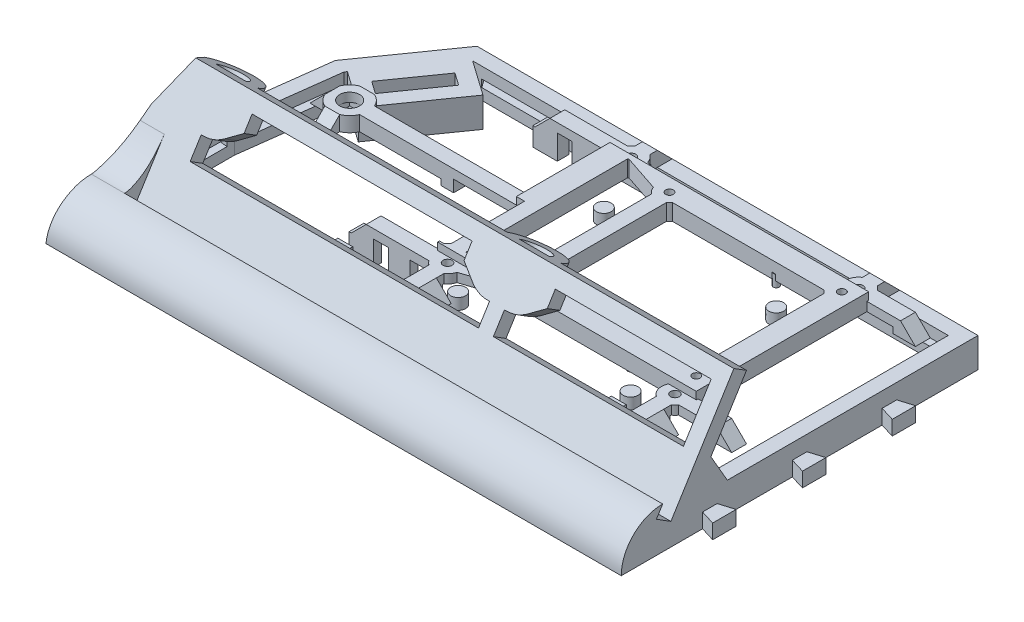
SolidWorks part; units mm, degrees
ref_plane "Front Plane" through (0, 0, 0) normal (0, 0, 1) x (1, 0, 0)
ref_plane "Top Plane" through (0, 0, 0) normal (0, 1, 0) x (1, 0, 0)
ref_plane "Right Plane" through (0, 0, 0) normal (1, 0, 0) x (0, 0, -1)
sketch "Sketch1" plane through (0, 0, 0) normal (1, 0, 0) x (0, 0, -1)
  line L0 (-2.7566, 6.4392) -> (-12.99, 6.4392) construction
  line L1 (-16.6958, -7.5) -> (103.3042, -7.5)
  line L2 (103.3042, -7.5) -> (103.3042, 2.5)
  line L3 (103.3042, 2.5) -> (18.9883, 2.5)
  line L4 (13.451, 12.0908) -> (25.437, 31.2723)
  line L5 (25.437, 31.2723) -> (21.1968, 33.9219)
  line L6 (21.1968, 33.9219) -> (0, 0)
  line L7 (0, 0) -> (-4.8763, 3.047)
  line L8 (25.437, 31.2723) -> (19.444, 21.6816) construction
  line L9 (-2.7566, 6.4392) -> (-4.8763, 3.047)
  line L10 (19.444, 21.6816) -> (13.451, 12.0908) construction
  line L11 (13.451, 12.0908) -> (7.4581, 2.5) construction
  line L12 (18.9883, 2.5) -> (7.4581, 2.5) construction
  line L13 (13.451, 12.0908) -> (18.9883, 2.5)
  arc A0 (-2.7566, 6.4392) -> (-16.6958, -7.5) centre (-2.7566, -7.5) ccw
  dimension "D10" = 58
  dimension "D1" = 4
  dimension "D2" = 5.75
  dimension "D3" = 40
  dimension "D4" = 7.5
  dimension "D5" = 120
  dimension "D6" = 10
  dimension "D7" = 5
  dimension "D8" = 60
  dimension "D9" = 58
extrude "Boss-Extrude1" add sketch "Sketch1" along normal blind 181 and the other way blind 12.5 contours L6 L7 L9 L1 L2 L3 L4 region at (0, 0.3543, -38.4922)
ref_plane "Plane1" through (0, -2.5, 0) normal (0, 1, 0) x (1, 0, 0)
sketch "Sketch4" plane through (0, 0, 0) normal (-1, 0, 0) x (0, 0, 1)
  line L0 (-21.1968, 33.9219) -> (0, 0) construction
  line L2 (-10.5984, 16.961) -> (0, 0)
  line L3 (0, 0) -> (4.8763, 3.047)
  line L4 (4.8763, 3.047) -> (2.7566, 6.4392)
  arc A0 (16.6958, -7.5) -> (2.7566, 6.4392) centre (2.7566, -7.5) ccw construction
  spline S0 degree 3 poles (2.7566, 6.4392) (0.7239, 6.4392) (-5.4135, 8.6634) (-10.5984, 16.961) knots 0 0 0 0 1 1 1 1
extrude "Boss-Extrude2" add sketch "Sketch4" along normal blind 12.5
sketch "Sketch3" plane through (0, 0, 0) normal (0, 0, 1) x (1, 0, 0)
  line L0 (0, 0) -> (0, 33.9219) construction
  line L1 (0, 33.9219) -> (-6.9073, 21.0423)
  line L2 (0, 33.9219) -> (-12.5, 33.9219)
  line L3 (-12.5, 33.9219) -> (181, 33.9219) construction
  line L4 (-6.9073, 21.0423) -> (-11.1296, 7.0505)
  line L5 (-12.5, 33.9219) -> (-12.5, -7.5)
  line L6 (-12.5, -7.5) -> (181, -7.5) construction
  line L7 (-11.1296, 7.0505) -> (-12.5, -7.5)
  arc A0 (-10.9929, 7.5036) -> (-11.174, 6.5794) centre (-11.1296, 7.0505) cw construction
  arc A1 (-6.6836, 21.4593) -> (-7.044, 20.5892) centre (-6.9073, 21.0423) cw construction
  spline S0 degree 2 poles (0, 33.9219) (-12.5, 15.097) (-12.5, -7.5) knots 0 0 0 1 1 1 construction
extrude "Cut-Extrude1" cut sketch "Sketch3" against normal blind 80 and the other way blind 80 contours L7 L4 L1 L2 L5 region at (-8.7764, 23.2458, 0)
sketch "Sketch5" plane through (0, 0, 0) normal (0, 1, 0) x (1, 0, 0)
  line B0 (-12.5, 103.3042) -> (12.5, 103.3042)
  line B1 (12.5, 103.3042) -> (-7.1997, 75.3013)
  line B2 (-7.1997, 75.3013) -> (-11.5261, 41.3377)
  line B3 (-11.5261, 41.3377) -> (-12.5, 7.1136)
  line B4 (-12.5, 103.3042) -> (-12.5, 7.1136)
sketch_block_instance "Block5-1"
sketch_block "Block5" parameters "D1"=25
extrude "Cut-Extrude2" cut sketch "Sketch5" against normal blind 10 and the other way blind 80
sketch "Sketch16" plane through (0, -7.5, 0) normal (0, -1, 0) x (1, 0, 0)
  line L0 (185.9, -9.1541) -> (181, -10.6541)
  line L1 (181, 16.6958) -> (181, -103.3042) construction
  line L2 (185.9, -9.1541) -> (185.9, -17.0541)
  line L3 (185.9, -17.0541) -> (181, -15.5541)
  line L4 (185.9, -69.5543) -> (181, -71.0543)
  line L5 (185.9, -69.5543) -> (185.9, -77.4543)
  line L6 (185.9, -77.4543) -> (181, -75.9543)
  line L7 (181, -40.8542) -> (185.9, -39.3542)
  line L8 (185.9, -39.3542) -> (185.9, -47.2542)
  line L9 (185.9, -47.2542) -> (181, -45.7542)
  line L10 (181, 16.6958) -> (185.9, -13.1041) construction
  line L11 (185.9, -13.1041) -> (185.9, -43.3042) construction
  line L12 (185.9, -43.3042) -> (185.9, -73.5043) construction
  line L13 (185.9, -73.5043) -> (181, -103.3042) construction
  line L14 (185.9, -43.3042) -> (181, -43.3042) construction
  line L15 (181, -10.6541) -> (181, -15.5541)
  line L16 (181, -40.8542) -> (181, -45.7542)
  line L17 (181, -71.0543) -> (181, -75.9543)
  line L18 (-12.5, 16.6958) -> (181, 16.6958) construction
  dimension "D1" = 4.9
  dimension "D2" = 4.9
  dimension "D3" = 7.9
  dimension "D4" = 29.7999
extrude "Boss-Extrude4" add sketch "Sketch16" against normal blind 4.9
sketch "Sketch18" plane through (0, 2.5, 0) normal (0, 1, 0) x (1, 0, 0)
  line L0 (20.6722, 88.851) -> (9.1647, 72.4932) construction
  line L1 (9.1647, 72.4932) -> (5.0753, 75.3701) construction
  line L2 (5.0753, 75.3701) -> (16.5828, 91.7279) construction
  line L3 (16.5828, 91.7279) -> (20.6722, 88.851) construction
  line L6 (12.5, 103.3042) -> (22.7236, 96.112) construction
  line L7 (22.7236, 96.112) -> (18.6275, 90.2894) construction
  line L8 (12.5, 103.3042) -> (-7.1997, 75.3013) construction
  line L9 (7.12, 73.9316) -> (3.0239, 68.1091) construction
  line L10 (3.0239, 68.1091) -> (-7.1997, 75.3013) construction
  line L11 (5.0056, 75.358) -> (16.5707, 91.7975)
  line L12 (16.5707, 91.7975) -> (20.7419, 88.8631)
  line L13 (20.7419, 88.8631) -> (9.1768, 72.4235)
  line L16 (9.1768, 72.4235) -> (5.0056, 75.358)
  line L18 (27.3633, 88.437) -> (27.3633, 77.0251) construction
  dimension "D1" = 20
  dimension "D2" = 5
  dimension "D3" = 12.5
  dimension "D5" = 35.126
  dimension "D4" = 0.05
extrude "Cut-Extrude15" cut sketch "Sketch18" against normal blind 5.1
sketch "Sketch19" plane through (0, 33.9219, -21.1968) normal (0, 0.848, -0.5299) x (1, 0, 0)
  line L0 (-11.5582, 5) -> (181, 5) construction
  line L1 (-1.421, 5) -> (2.529, 5)
  line L2 (12.629, 5) -> (16.579, 5)
  line L3 (100.579, 5) -> (104.529, 5)
  line L5 (114.629, 5) -> (118.579, 5)
  arc A0 (16.579, 5) -> (-1.421, 5) centre (7.579, 5) ccw
  arc A1 (12.629, 5) -> (2.529, 5) centre (7.579, 5) ccw
  arc A2 (114.629, 5) -> (104.529, 5) centre (109.579, 5) ccw
  arc A3 (100.579, 5) -> (118.579, 5) centre (109.579, 5) cw
  dimension "D1" = 10.1
  dimension "D2" = 18
  dimension "D4" = 102
  dimension "D3" = 3.95
extrude "Boss-Extrude5" add sketch "Sketch19" against normal blind 7.6 separate body
sketch "Sketch21" plane through (0, -2.6496, -4.2402) normal (0, -0.5299, -0.848) x (-1, 0, 0)
  line L0 (-7.579, 32.4) -> (-7.579, 29.4)
  line L1 (-16.579, 32.4) -> (1.421, 32.4) construction
  line L2 (-16.579, 32.4) -> (-15.2457, 31.4)
  line L3 (-7.579, 29.4) -> (-9.2457, 29.4)
  line L5 (-16.579, 32.4) -> (-7.579, 32.4)
  arc A0 (-9.2457, 29.4) -> (-15.2457, 31.4) centre (-9.2457, 39.4) cw
  dimension "D2" = 10
  dimension "D1" = 3
revolve "Revolve1" add sketch "Sketch21" angle 180 about L0 reverse direction yes
sketch "Sketch22" plane through (0, 0, 0) normal (1, 0, 0) x (0, 0, -1)
  line L0 (21.1968, 33.9219) -> (71.4824, 2.5) construction
  line L1 (103.3042, 2.5) -> (18.9883, 2.5) construction
  line L2 (33.0694, 26.5031) -> (25.437, 31.2723) construction
  point P7 (25.437, 31.2723)
  point P10 (71.4824, 2.5)
  dimension "D1" = 54.2957
sketch "Sketch24" plane through (0, 33.9219, -21.1968) normal (0, 0.848, -0.5299) x (1, 0, 0)
  line L0 (7.579, 5) -> (7.579, 128.2627) construction
  line L6 (2.529, 5) -> (12.629, 5) construction
  point P3 (7.579, 5)
sketch "Sketch25" plane through (0, 2.5, 0) normal (0, 1, 0) x (1, 0, 0)
  line L0 (16.5707, 91.7975) -> (9.1768, 72.4235) construction
  line L1 (7.579, -169584.1822) -> (7.579, 169739.5889) construction
  point P6 (12.8737, 82.1105)
  dimension "D1" = 5.2947
sketch "Sketch26" plane through (0, -2.6496, -4.2402) normal (0, -0.5299, -0.848) x (-1, 0, 0)
  line L0 (-109.579, 32.4) -> (-109.579, 29.4)
  line L2 (-118.579, 32.4) -> (-117.2457, 31.4)
  line L3 (-109.579, 29.4) -> (-111.2457, 29.4)
  line L5 (-118.579, 32.4) -> (-109.579, 32.4)
  line L6 (-118.579, 32.4) -> (-100.579, 32.4) construction
  arc A0 (-111.2457, 29.4) -> (-117.2457, 31.4) centre (-111.2457, 39.4) cw
  dimension "D2" = 10
  dimension "D1" = 3
revolve "Revolve2" add sketch "Sketch26" angle 180 about L0 reverse direction yes
sketch "Sketch33" plane through (0, -2.6496, -4.2402) normal (0, -0.5299, -0.848) x (-1, 0, 0)
  line L1 (-176, 35) -> (-123.579, 35)
  line L2 (-176, 35) -> (-176, 17.3815)
  line L3 (-176, 17.3815) -> (-112.079, 17.3815)
  line L4 (-21.579, 35) -> (-21.579, 29.9)
  line L5 (-118.579, 40) -> (-181, 40) construction
  line L6 (9.6086, 17.3815) -> (-181, 17.3815) construction
  line L7 (-123.579, 35) -> (-123.579, 29.9)
  line L8 (-118.579, 32.4) -> (-118.579, 40) construction
  line L9 (-95.579, 29.9) -> (-95.579, 35)
  line L10 (-100.579, 32.4) -> (-100.579, 40) construction
  line L11 (-123.579, 29.9) -> (-118.9124, 26.4)
  line L12 (-112.9124, 24.4) -> (-112.079, 24.4)
  line L13 (-100.2457, 26.4) -> (-95.579, 29.9)
  line L14 (-123.579, 29.9) -> (-95.579, 29.9) construction
  line L15 (-118.579, 32.4) -> (-117.2457, 31.4) construction
  line L16 (-100.579, 32.4) -> (-101.9124, 31.4) construction
  line L17 (-107.9124, 29.4) -> (-111.2457, 29.4) construction
  line L18 (2.038, 26.6128) -> (0.1213, 30.8271) construction
  line L19 (-112.079, 24.4) -> (-112.079, 17.3815)
  line L20 (-107.079, 24.4) -> (-106.2457, 24.4)
  line L21 (-107.079, 24.4) -> (-107.079, 17.3815)
  line L22 (-107.079, 17.3815) -> (-10.079, 17.3815)
  line L23 (-21.579, 29.9) -> (-16.9124, 26.4)
  line L24 (-10.9124, 24.4) -> (-10.079, 24.4)
  line L25 (-10.079, 24.4) -> (-10.079, 17.3815)
  line L26 (-5.9124, 29.4) -> (-9.2457, 29.4) construction
  line L27 (-16.579, 32.4) -> (-15.2457, 31.4) construction
  line L28 (-7.579, 29.4) -> (-7.579, 17.3815) construction
  line L29 (-16.579, 32.4) -> (-16.579, 40) construction
  line L30 (2.038, 26.6128) -> (1.7543, 26.4)
  line L31 (-4.2457, 24.4) -> (-5.079, 24.4)
  line L32 (-5.079, 24.4) -> (-5.079, 17.3815)
  line L33 (4.4675, 17.3815) -> (2.1913, 26.2757)
  line L34 (2.1913, 26.2757) -> (2.038, 26.6128)
  line L35 (6.9073, 27.9369) -> (9.6086, 17.3815) construction
  line L36 (1.421, 40) -> (6.9073, 27.9369) construction
  line L37 (2.1913, 26.2757) -> (6.9073, 27.9369) construction
  line L38 (1.421, 32.4) -> (0.0876, 31.4) construction
  line L39 (-95.579, 35) -> (-21.579, 35)
  line L40 (-181, 17.3815) -> (-181, 40) construction
  arc A0 (-106.2457, 24.4) -> (-100.2457, 26.4) centre (-106.2457, 34.4) ccw
  arc A1 (-118.9124, 26.4) -> (-112.9124, 24.4) centre (-112.9124, 34.4) ccw
  arc A2 (1.7543, 26.4) -> (-4.2457, 24.4) centre (-4.2457, 34.4) cw
  arc A3 (-16.9124, 26.4) -> (-10.9124, 24.4) centre (-10.9124, 34.4) ccw
  arc A4 (3.431, 21.4318) -> (0.1213, 30.8271) centre (2.1913, 26.2757) ccw construction
  point P18 (-95.579, 32.45)
  point P52 (-0.9124, 24.4)
  point P55 (-14.2457, 24.4)
  point P59 (6.9073, 27.9369)
  line M30 (-181, 17.3815) -> (9.6086, 17.3815)
  dimension "D3" = 10
  dimension "D11" = 10
  dimension "D1" = 5
  dimension "D2" = 5
  dimension "D4" = 5
  dimension "D5" = 5
  dimension "D6" = 5
  dimension "D7" = 5
  dimension "D8" = 5
  dimension "D9" = 2.5
  dimension "D10" = 5
  dimension "D12" = 5
  dimension "D13" = 5
  dimension "D14" = 5
extrude "Cut-Extrude21" cut sketch "Sketch33" against normal blind 5 contours A3 L23 L4 L39 L9 L13 A0 L20 L21 L25 L24 M30 | A1 L11 L7 L1 L2 L19 L12 M30 region at (58.579, 19.0794, -17.818) region at (146.6729, 19.2071, -17.8978)
sketch "Sketch35" plane through (0, 2.5, 0) normal (0, 1, 0) x (1, 0, 0)
  line L0 (12.5, 103.3042) -> (-7.1997, 75.3013)
  line L1 (-7.1997, 75.3013) -> (-11.5261, 41.3377)
  line L2 (12.5, 103.3042) -> (181, 103.3042)
  line L3 (181, 103.3042) -> (181, 23.9883)
  line L4 (-11.5582, 18.9883) -> (181, 18.9883) construction
  line L5 (-11.5582, 23.9883) -> (-11.5261, 41.3377)
  line L6 (-11.5582, 18.9883) -> (-11.5582, 40.2092) construction
  line L9 (181, 23.9883) -> (-11.5582, 23.9883)
  point P11 (-11.5582, 23.9883)
  point P13 (0, 0)
  dimension "D1" = 5
extrude "Boss-Extrude7" add sketch "Sketch35" along normal blind 5
sketch "Sketch34" plane through (0, -7.5, 0) normal (0, -1, 0) x (1, 0, 0)
  line L0 (115.825, -18.9883) -> (115.825, -103.3042) construction
  line L1 (65.65, -26.2462) -> (166, -26.2462) construction
  line L2 (65.65, -26.2462) -> (65.65, -44.2462) construction
  line L3 (65.65, -96.0462) -> (166, -96.0462) construction
  line L4 (166, -26.2462) -> (166, -96.0462) construction
  line L5 (181, -75.9543) -> (181, -103.3042) construction
  line L6 (65.65, -26.2462) -> (166, -96.0462) construction
  line L7 (12.5, -103.3042) -> (181, -103.3042) construction
  line L9 (21.65, -64.2962) -> (21.65, -69.6462) construction
  line L10 (53.45, -69.6462) -> (53.45, -98.0462) construction
  line L11 (65.65, -44.2462) -> (58.05, -44.2462) construction
  line L12 (65.45, -26.0462) -> (166.2, -26.0462)
  line L13 (65.65, -87.5462) -> (58.05, -87.5462) construction
  line L14 (166.2, -26.0462) -> (166.2, -96.2462)
  line L15 (53.45, -24.2462) -> (58.05, -24.2462) construction
  line L16 (53.45, -24.2462) -> (53.45, -52.6462) construction
  line L17 (53.45, -98.0462) -> (58.05, -98.0462) construction
  line L18 (58.05, -24.2462) -> (58.05, -44.2462) construction
  line L19 (21.65, -52.6462) -> (53.45, -52.6462) construction
  line L20 (21.65, -52.6462) -> (21.65, -57.9962) construction
  line L21 (21.65, -69.6462) -> (53.45, -69.6462) construction
  line L22 (65.45, -96.2462) -> (166.2, -96.2462)
  line L23 (21.65, -57.9962) -> (8.65, -57.9962) construction
  line L24 (65.45, -87.7462) -> (65.45, -96.2462)
  line L25 (21.65, -64.2962) -> (8.65, -64.2962) construction
  line L26 (8.65, -57.9962) -> (8.65, -64.2962) construction
  line L27 (58.05, -87.5462) -> (58.05, -98.0462) construction
  line L28 (65.65, -87.5462) -> (65.65, -96.0462) construction
  line L29 (65.45, -87.7462) -> (58.25, -87.7462)
  line L30 (58.25, -87.7462) -> (58.25, -98.2462)
  line L31 (53.25, -98.2462) -> (58.25, -98.2462)
  line L32 (53.25, -69.8462) -> (53.25, -98.2462)
  line L33 (21.45, -69.8462) -> (53.25, -69.8462)
  line L34 (21.45, -64.4962) -> (21.45, -69.8462)
  line L35 (21.45, -64.4962) -> (8.45, -64.4962)
  line L36 (8.45, -57.7962) -> (8.45, -64.4962)
  line L37 (21.45, -57.7962) -> (8.45, -57.7962)
  line L38 (21.45, -52.4462) -> (21.45, -57.7962)
  line L39 (21.45, -52.4462) -> (53.25, -52.4462)
  line L40 (53.25, -24.0462) -> (53.25, -52.4462)
  line L41 (53.25, -24.0462) -> (58.25, -24.0462)
  line L42 (58.25, -24.0462) -> (58.25, -44.0462)
  line L43 (65.45, -44.0462) -> (58.25, -44.0462)
  line L44 (65.45, -26.0462) -> (65.45, -44.0462)
  point P9 (115.825, -61.1462)
  point P10 (66.8992, -96.0462)
  point P12 (0, 0)
  point P15 (115.825, -61.1462)
  point P18 (28.3358, -52.7545)
  point P19 (0, 0)
  point P53 (0, 0)
  dimension "D1" = 100.35
  dimension "D2" = 69.8
  dimension "D3" = 18
  dimension "D4" = 8.5
  dimension "D5" = 7.6
  dimension "D6" = 12.2
  dimension "D7" = 2
  dimension "D8" = 2
  dimension "D9" = 17
  dimension "D10" = 28.4
  dimension "D11" = 6.3
  dimension "D12" = 5.35
  dimension "D13" = 13
  dimension "D14" = 44
  dimension "D15" = 15
  dimension "D16" = 0.2
extrude "Cut-Extrude23" cut sketch "Sketch34" against normal blind 12
sketch "Sketch36" plane through (0, 4.5, 0) normal (0, 1, 0) x (1, 0, 0)
  line L0 (75.625, 92.0462) -> (75.625, 30.2462) construction
  line L1 (65.625, 96.0462) -> (166.025, 96.0462) construction
  line L2 (65.625, 96.0462) -> (65.625, 26.2462) construction
  line L3 (65.625, 26.2462) -> (166.025, 26.2462) construction
  line L4 (166.025, 96.0462) -> (166.025, 26.2462) construction
  line L5 (75.625, 92.0462) -> (152.125, 92.0462) construction
  line L6 (152.125, 92.0462) -> (152.125, 30.2462) construction
  line L7 (152.125, 30.2462) -> (75.625, 30.2462) construction
  line L8 (65.625, 61.1462) -> (75.625, 61.1462) construction
  line L9 (65.625, 96.0462) -> (166.025, 26.2462) construction
  line L10 (166.2, 96.2462) -> (65.45, 26.0462) construction
  circle A0 centre (75.625, 92.0462) radius 1.5
  circle A1 centre (152.125, 92.0462) radius 1.5
  circle A2 centre (75.625, 30.2462) radius 1.5
  circle A3 centre (152.125, 30.2462) radius 1.5
  point P16 (115.825, 61.1462)
  point P17 (115.825, 61.1462)
  dimension "D3" = 3
  dimension "D1" = 100.4
  dimension "D2" = 69.8
  dimension "D4" = 61.8
  dimension "D5" = 76.5
  dimension "D6" = 13.9
  dimension "D7" = 10
extrude "Cut-Extrude25" cut sketch "Sketch36" along normal blind 10
sketch "Sketch37" plane through (0, 7.5, 0) normal (0, 1, 0) x (1, 0, 0)
  circle A0 centre (75.625, 92.0462) radius 3
  circle A1 centre (152.125, 92.0462) radius 3
  circle A2 centre (152.125, 30.2462) radius 3
  circle A3 centre (75.625, 30.2462) radius 3
  dimension "D1" = 6
sketch "Sketch39" plane through (0, 7.5, 0) normal (0, 1, 0) x (1, 0, 0)
  line L0 (75.625, 92.0462) -> (152.125, 30.2462) construction
  line L1 (70.375, 90.1462) -> (157.375, 90.1462)
  line L2 (70.375, 90.1462) -> (70.375, 32.1462)
  line L3 (70.375, 32.1462) -> (157.375, 32.1462)
  line L4 (157.375, 90.1462) -> (157.375, 32.1462)
  line L6 (157.375, 90.1462) -> (70.375, 32.1462) construction
  point P4 (113.875, 61.1462)
  point P5 (113.875, 61.1462)
  dimension "D1" = 87
  dimension "D2" = 58
extrude "Boss-Extrude8" add sketch "Sketch39" along normal blind 2.5
sketch "Sketch40" plane through (0, 10, 0) normal (0, 1, 0) x (1, 0, 0)
  line L1 (94.875, 85.6462) -> (152.875, 85.6462) construction
  line L2 (94.875, 85.6462) -> (94.875, 36.6462) construction
  line L3 (94.875, 36.6462) -> (152.875, 36.6462) construction
  line L4 (152.875, 85.6462) -> (152.875, 36.6462) construction
  line L6 (157.375, 90.1462) -> (70.375, 90.1462) construction
  line L7 (157.375, 32.1462) -> (157.375, 90.1462) construction
  circle A0 centre (94.875, 85.6462) radius 1.3
  circle A1 centre (94.875, 36.6462) radius 1.3
  circle A2 centre (152.875, 36.6462) radius 1.3
  circle A3 centre (152.875, 85.6462) radius 1.3
  dimension "D5" = 2.6
  dimension "D1" = 58
  dimension "D2" = 49
  dimension "D3" = 4.5
  dimension "D4" = 4.5
extrude "Cut-Extrude28" cut sketch "Sketch40" against normal blind 10
sketch "Sketch41" plane through (0, 4.5, 0) normal (0, -1, 0) x (1, 0, 0)
  line L1 (96.2808, -39.0812) -> (97.6867, -36.6462)
  line L2 (97.6867, -36.6462) -> (96.2808, -34.2112)
  line L3 (96.2808, -34.2112) -> (93.4692, -34.2112)
  line L4 (93.4692, -34.2112) -> (92.0633, -36.6462)
  line L5 (92.0633, -36.6462) -> (93.4692, -39.0812)
  line L6 (93.4692, -39.0812) -> (96.2808, -39.0812)
  line L7 (151.4692, -39.0812) -> (154.2808, -39.0812)
  line L8 (154.2808, -39.0812) -> (155.6867, -36.6462)
  line L9 (155.6867, -36.6462) -> (154.2808, -34.2112)
  line L10 (154.2808, -34.2112) -> (151.4692, -34.2112)
  line L11 (151.4692, -34.2112) -> (150.0633, -36.6462)
  line L12 (150.0633, -36.6462) -> (151.4692, -39.0812)
  line L13 (151.4692, -83.2112) -> (150.0633, -85.6462)
  line L14 (150.0633, -85.6462) -> (151.4692, -88.0812)
  line L15 (151.4692, -88.0812) -> (154.2808, -88.0812)
  line L16 (154.2808, -88.0812) -> (155.6867, -85.6462)
  line L17 (155.6867, -85.6462) -> (154.2808, -83.2112)
  line L18 (154.2808, -83.2112) -> (151.4692, -83.2112)
  line L19 (96.2808, -83.2112) -> (93.4692, -83.2112)
  line L20 (93.4692, -83.2112) -> (92.0633, -85.6462)
  line L21 (92.0633, -85.6462) -> (93.4692, -88.0812)
  line L22 (93.4692, -88.0812) -> (96.2808, -88.0812)
  line L23 (96.2808, -88.0812) -> (97.6867, -85.6462)
  line L24 (97.6867, -85.6462) -> (96.2808, -83.2112)
  circle A0 centre (94.875, -36.6462) radius 2.435 construction
  circle A1 centre (152.875, -36.6462) radius 2.435 construction
  circle A2 centre (152.875, -85.6462) radius 2.435 construction
  circle A3 centre (94.875, -85.6462) radius 2.435 construction
  point P28 (150.9697, -39.9464)
  dimension "D1" = 4.87
extrude "Cut-Extrude29" cut sketch "Sketch41" against normal blind 2.5
sketch "Sketch42" plane through (0, 4.5, 0) normal (0, -1, 0) x (1, 0, 0)
  line L0 (21.45, -69.8462) -> (53.25, -69.8462) construction
  line L1 (21.45, -52.4462) -> (49.25, -52.4462)
  line L2 (21.45, -52.4462) -> (21.45, -57.7962)
  line L3 (21.45, -69.8462) -> (49.25, -69.8462)
  line L4 (49.25, -52.4462) -> (49.25, -69.8462)
  line L5 (53.25, -24.0462) -> (53.25, -52.4462) construction
  line L6 (21.45, -57.7962) -> (8.45, -57.7962) construction
  line L7 (15.15, -57.7962) -> (21.45, -57.7962)
  line L8 (15.15, -57.7962) -> (15.15, -64.4962)
  line L9 (15.15, -64.4962) -> (21.45, -64.4962)
  line L11 (8.45, -57.7962) -> (8.45, -64.4962) construction
  line L12 (21.45, -64.4962) -> (21.45, -69.8462)
  dimension "D1" = 4
  dimension "D2" = 6.7
extrude "Boss-Extrude9" add sketch "Sketch42" along normal blind 4
sketch "Sketch43" plane through (0, 2.5, 0) normal (0, 1, 0) x (1, 0, 0)
  line L0 (12.5, 103.3042) -> (181, 103.3042)
  line L1 (181, 23.9883) -> (168.7, 23.9883)
  line L3 (12.5, 103.3042) -> (-7.1997, 75.3013) construction
  line L4 (181, 103.3042) -> (12.5, 103.3042) construction
  line L5 (50.75, 23.9883) -> (-11.5582, 23.9883)
  line L6 (181, 23.9883) -> (181, 103.3042) construction
  line L7 (-11.5582, 23.9883) -> (181, 23.9883) construction
  line L8 (50.75, 98.3042) -> (168.7, 98.3042)
  line L228 (12.5, 103.3042) -> (-7.1997, 75.3013)
  line L229 (-7.1997, 75.3013) -> (-11.5261, 41.3377)
  line L230 (-11.5261, 41.3377) -> (-11.5582, 23.9883)
  line L232 (-11.5261, 41.3377) -> (-11.5582, 23.9883) construction
  line L235 (181, 23.9883) -> (181, 103.3042)
  line L246 (50.75, 21.5462) -> (60.75, 21.5462)
  line L247 (50.75, 49.9462) -> (50.75, 21.5462)
  line L248 (60.75, 21.5462) -> (60.75, 41.5462)
  line L249 (62.95, 23.5462) -> (168.7, 23.5462)
  line L250 (168.7, 23.5462) -> (168.7, 98.7462)
  line L251 (168.7, 98.7462) -> (62.95, 98.7462)
  line L252 (60.75, 90.2462) -> (60.75, 100.7462)
  line L253 (60.75, 100.7462) -> (50.75, 100.7462)
  line L254 (50.75, 100.7462) -> (50.75, 72.3462)
  line L255 (50.75, 72.3462) -> (18.95, 72.3462)
  line L256 (18.95, 72.3462) -> (18.95, 66.9962)
  line L257 (18.95, 66.9962) -> (5.95, 66.9962)
  line L258 (5.95, 66.9962) -> (5.95, 55.2962)
  line L259 (5.95, 55.2962) -> (18.95, 55.2962)
  line L260 (18.95, 55.2962) -> (18.95, 49.9462)
  line L261 (18.95, 49.9462) -> (50.75, 49.9462)
  line L263 (50.75, 49.9462) -> (50.75, 23.9883)
  line L266 (168.7, 23.9883) -> (168.7, 98.3042)
  line L270 (50.75, 98.3042) -> (50.75, 72.3462)
  line L271 (50.75, 72.3462) -> (18.95, 72.3462)
  line L272 (18.95, 72.3462) -> (18.95, 66.9962)
  line L273 (18.95, 66.9962) -> (5.95, 66.9962)
  line L274 (5.95, 66.9962) -> (5.95, 55.2962)
  line L275 (5.95, 55.2962) -> (18.95, 55.2962)
  line L276 (18.95, 55.2962) -> (18.95, 49.9462)
  line L277 (18.95, 49.9462) -> (50.75, 49.9462)
  line L279 (60.75, 41.5462) -> (62.95, 41.5462)
  line L281 (62.95, 41.5462) -> (62.95, 23.5462)
  line L283 (62.95, 98.7462) -> (62.95, 90.2462)
  line L285 (62.95, 90.2462) -> (60.75, 90.2462)
  dimension "D2" = 0
  dimension "D4" = 5
  dimension "D1" = 2.5
extrude "Cut-Extrude30" cut sketch "Sketch43" along normal blind 5
sketch "Sketch45" plane through (0, 4.5, 0) normal (0, -1, 0) x (1, 0, 0)
  line L0 (21.45, -57.7962) -> (8.45, -57.7962) construction
  line L1 (15.15, -57.7962) -> (15.15, -64.4962) construction
  line L2 (8.45, -64.4962) -> (15.15, -64.4962) construction
  circle A0 centre (11.8, -61.1462) radius 3.35
extrude "Cut-Extrude32" cut sketch "Sketch45" against normal blind 5
sketch "Sketch44" plane through (0, 10, 0) normal (0, 1, 0) x (1, 0, 0)
  line L0 (75.625, 92.0462) -> (94.875, 85.6462) construction
  line L1 (75.625, 30.2462) -> (94.875, 36.6462) construction
  line L2 (152.125, 92.0462) -> (152.875, 85.6462) construction
  line L3 (94.875, 85.6462) -> (152.875, 85.6462) construction
  line L4 (152.875, 36.6462) -> (152.125, 30.2462) construction
  line L5 (152.875, 85.6462) -> (152.875, 36.6462) construction
  line L6 (152.875, 36.6462) -> (94.875, 36.6462) construction
  line L7 (94.875, 36.6462) -> (94.875, 85.6462) construction
  line L8 (75.625, 92.0462) -> (75.625, 103.3042) construction
  line L9 (181, 103.3042) -> (12.5, 103.3042) construction
  line L10 (152.125, 92.0462) -> (152.125, 103.3042) construction
  line L11 (152.125, 92.0462) -> (181, 92.0462) construction
  line L12 (181, 18.9883) -> (181, 103.3042) construction
  line L13 (152.125, 30.2462) -> (152.125, 18.9883) construction
  line L14 (152.125, 30.2462) -> (181, 30.2462) construction
  line L15 (-11.5582, 18.9883) -> (181, 18.9883) construction
  line L16 (75.625, 30.2462) -> (75.625, 18.9883) construction
  line L17 (75.625, 30.2462) -> (-11.5582, 30.2462) construction
  line L18 (-11.5582, 18.9883) -> (-11.5582, 40.2092) construction
  line L19 (75.625, 92.0462) -> (4.5802, 92.0462) construction
  line L20 (12.5, 103.3042) -> (-7.1997, 75.3013) construction
  line L21 (176, 98.3042) -> (15.0959, 98.3042) construction
  line L22 (19.6074, 98.3042) -> (24.9493, 94.5462)
  line L23 (29.8655, 89.5462) -> (14.3, 67.4202)
  line L24 (-2.5739, 72.047) -> (7.0046, 65.3087)
  line L25 (9.1768, 72.4235) -> (20.7419, 88.8631) construction
  line L26 (-2.3966, 73.439) -> (-6.5265, 41.017) construction
  line L27 (18.6563, 90.3303) -> (22.7236, 96.112) construction
  line L28 (20.7419, 88.8631) -> (16.5707, 91.7975) construction
  line L29 (14.9594, 80.6433) -> (20.741, 76.576) construction
  line L30 (9.1768, 72.4235) -> (20.7419, 88.8631) construction
  line L31 (19.6074, 98.3042) -> (12.5, 103.3042) construction
  line L32 (5.0056, 75.358) -> (9.1768, 72.4235) construction
  line L33 (78.125, 88.3046) -> (78.125, 33.9879)
  line L34 (75.625, 94.5462) -> (4.5802, 94.5462) construction
  line L35 (73.125, 92.0462) -> (73.125, 103.3042) construction
  line L36 (73.125, 92.0462) -> (73.125, 30.2462) construction
  line L37 (71.8833, 89.5462) -> (29.8655, 89.5462)
  line L38 (74.8363, 89.6739) -> (94.0863, 83.2739) construction
  line L40 (79.9643, 93.2381) -> (92.3438, 89.1223)
  line L41 (78.125, 92.0462) -> (78.125, 103.3042) construction
  line L42 (75.625, 27.7462) -> (-11.5582, 27.7462) construction
  line L43 (-6.5456, 27.7462) -> (-6.551, 23.9883)
  line L44 (-6.5265, 41.017) -> (-6.551, 23.9883) construction
  line L45 (176, 27.7462) -> (176, 23.9883)
  line L46 (181, 103.3042) -> (12.5, 103.3042) construction
  line L47 (12.5, 103.3042) -> (-7.1997, 75.3013) construction
  line L48 (-7.1997, 75.3013) -> (-11.5261, 41.3377) construction
  line L49 (-11.5261, 41.3377) -> (-11.5582, 18.9883) construction
  line L50 (-11.5582, 18.9883) -> (181, 18.9883) construction
  line L51 (181, 103.3042) -> (181, 18.9883) construction
  line L52 (-2.5739, 72.047) -> (-3.644, 63.6462)
  line L53 (-6.5265, 41.017) -> (-6.5384, 32.7462)
  line L54 (-6.551, 23.9883) -> (73.125, 23.9883)
  line L55 (176, 98.3042) -> (176, 94.5462)
  line L56 (176, 98.3042) -> (154.625, 98.3042)
  line L57 (92.375, 40.1448) -> (92.375, 82.1477)
  line L58 (75.625, 92.0462) -> (75.625, 30.2462) construction
  line L59 (149.3764, 39.1462) -> (98.3736, 39.1462)
  line L60 (73.125, 26.5046) -> (73.125, 23.9883)
  line L61 (73.125, 88.3046) -> (73.125, 63.6462)
  line L62 (79.9643, 29.0544) -> (92.3438, 33.1701)
  line L63 (97.375, 40.1448) -> (97.375, 82.1477)
  line L64 (78.3868, 88.4935) -> (90.7664, 84.3777)
  line L65 (78.125, 95.7879) -> (78.125, 98.3042)
  line L66 (71.8833, 94.5462) -> (24.9493, 94.5462)
  line L67 (98.3736, 88.1462) -> (149.3764, 88.1462)
  line L68 (155.375, 85.6462) -> (155.375, 36.6462) construction
  line L69 (155.8667, 32.7462) -> (176, 32.7462)
  line L70 (149.625, 26.5046) -> (149.625, 23.9883)
  line L71 (154.625, 95.7879) -> (154.625, 98.3042)
  line L72 (149.625, 92.0462) -> (149.625, 103.3042) construction
  line L73 (98.3736, 83.1462) -> (149.3764, 83.1462)
  line L74 (176, 98.3042) -> (176, 23.9883) construction
  line L75 (176, 89.5462) -> (176, 32.7462)
  line L76 (71.8833, 27.7462) -> (-6.5456, 27.7462)
  line L77 (78.125, 26.5046) -> (78.125, 23.9883)
  line L78 (78.125, 30.2462) -> (78.125, 18.9883) construction
  line L79 (154.625, 23.9883) -> (176, 23.9883)
  line L80 (73.125, 98.3042) -> (19.6074, 98.3042)
  line L81 (73.125, 30.2462) -> (73.125, 18.9883) construction
  line L82 (73.125, 95.7879) -> (73.125, 98.3042)
  line L83 (78.125, 23.9883) -> (149.625, 23.9883)
  line L84 (149.625, 98.3042) -> (78.125, 98.3042)
  line L85 (11.8, 61.1462) -> (-9.0028, 61.1462) construction
  line L86 (155.8667, 94.5462) -> (176, 94.5462)
  line L87 (11.8, 61.1462) -> (11.8, 30.2462) construction
  line L88 (155.8667, 89.5462) -> (176, 89.5462)
  line L89 (155.375, 82.1477) -> (155.375, 40.1448)
  line L90 (11.8, 61.1462) -> (75.625, 61.1462) construction
  line L91 (11.8, 61.1462) -> (11.8, 92.0462) construction
  line L92 (149.625, 95.7879) -> (149.625, 98.3042)
  line L93 (15.0959, 98.3042) -> (-2.3966, 73.439) construction
  line L94 (-6.551, 23.9883) -> (176, 23.9883) construction
  line L95 (76.4137, 27.8739) -> (95.6637, 34.2739) construction
  line L96 (71.8833, 32.7462) -> (14.3, 32.7462)
  line L97 (78.3868, 33.799) -> (90.7664, 37.9148)
  line L98 (97.375, 36.6462) -> (97.375, 85.6462) construction
  line L99 (149.625, 30.2462) -> (149.625, 18.9883) construction
  line L100 (14.3, 61.1462) -> (14.3, 92.0462) construction
  line L101 (7.0912, 73.8907) -> (3.0239, 68.1091) construction
  line L102 (154.625, 26.5046) -> (154.625, 23.9883)
  line L103 (155.8667, 27.7462) -> (176, 27.7462)
  line L104 (149.3764, 34.1462) -> (98.3736, 34.1462)
  line L105 (150.375, 82.1477) -> (150.375, 40.1448)
  line L106 (73.125, 58.6462) -> (73.125, 33.9879)
  line L107 (14.3, 66.9834) -> (14.3, 67.4202)
  line L108 (9.3, 32.7462) -> (-6.5384, 32.7462)
  line L114 (-4.2809, 58.6462) -> (-6.5265, 41.017)
  line L115 (5.9628, 63.6462) -> (-3.644, 63.6462)
  line L117 (5.9628, 58.6462) -> (-4.2809, 58.6462)
  line L118 (9.3, 55.3091) -> (9.3, 32.7462)
  line L120 (14.3, 55.3091) -> (14.3, 32.7462)
  line L122 (17.6372, 58.6462) -> (73.125, 58.6462)
  line L124 (17.6372, 63.6462) -> (73.125, 63.6462)
  arc A0 (98.3736, 88.1462) -> (92.3438, 89.1223) centre (94.875, 85.6462) ccw
  arc A1 (97.375, 82.1477) -> (98.3736, 83.1462) centre (94.875, 85.6462) ccw
  arc A2 (92.375, 40.1448) -> (90.7664, 37.9148) centre (94.875, 36.6462) ccw
  arc A3 (149.3764, 34.1462) -> (149.5411, 33.9305) centre (152.875, 36.6462) ccw
  arc A4 (71.8833, 89.5462) -> (73.125, 88.3046) centre (75.625, 92.0462) ccw
  arc A5 (149.625, 95.7879) -> (149.5411, 88.362) centre (152.125, 92.0462) ccw
  arc A6 (154.625, 26.5046) -> (155.8667, 27.7462) centre (152.125, 30.2462) ccw
  arc A7 (78.125, 26.5046) -> (79.9643, 29.0544) centre (75.625, 30.2462) ccw
  circle A8 centre (94.875, 85.6462) radius 1.3 construction
  circle A9 centre (75.625, 92.0462) radius 1.5 construction
  arc A10 (73.125, 95.7879) -> (71.8833, 94.5462) centre (75.625, 92.0462) ccw
  arc A11 (78.125, 88.3046) -> (78.3868, 88.4935) centre (75.625, 92.0462) ccw
  arc A12 (79.9643, 93.2381) -> (78.125, 95.7879) centre (75.625, 92.0462) ccw
  arc A13 (78.3868, 33.799) -> (78.125, 33.9879) centre (75.625, 30.2462) ccw
  arc A14 (73.125, 33.9879) -> (71.8833, 32.7462) centre (75.625, 30.2462) ccw
  arc A15 (71.8833, 27.7462) -> (73.125, 26.5046) centre (75.625, 30.2462) ccw
  arc A16 (92.3438, 33.1701) -> (98.3736, 34.1462) centre (94.875, 36.6462) ccw
  arc A17 (98.3736, 39.1462) -> (97.375, 40.1448) centre (94.875, 36.6462) ccw
  arc A18 (150.375, 40.1448) -> (149.3764, 39.1462) centre (152.875, 36.6462) ccw
  arc A19 (155.8667, 32.7462) -> (155.4907, 33.2333) centre (152.125, 30.2462) ccw
  arc A20 (155.8667, 94.5462) -> (154.625, 95.7879) centre (152.125, 92.0462) ccw
  arc A21 (155.4907, 33.2333) -> (155.375, 40.1448) centre (152.875, 36.6462) ccw
  arc A22 (149.5411, 33.9305) -> (149.625, 26.5046) centre (152.125, 30.2462) ccw
  arc A23 (155.4907, 89.0592) -> (155.8667, 89.5462) centre (152.125, 92.0462) ccw
  arc A24 (155.375, 82.1477) -> (155.4907, 89.0592) centre (152.875, 85.6462) ccw
  arc A25 (149.3764, 83.1462) -> (150.375, 82.1477) centre (152.875, 85.6462) ccw
  arc A26 (90.7664, 84.3777) -> (92.375, 82.1477) centre (94.875, 85.6462) ccw
  arc A27 (149.5411, 88.362) -> (149.3764, 88.1462) centre (152.875, 85.6462) ccw
  arc A28 (5.9628, 58.6462) -> (9.3, 55.3091) centre (11.8, 61.1462) ccw
  circle A29 centre (11.8, 61.1462) radius 3.35 construction
  arc A30 (7.0046, 65.3087) -> (5.9628, 63.6462) centre (11.8, 61.1462) ccw
  arc A31 (14.3, 55.3091) -> (17.6372, 58.6462) centre (11.8, 61.1462) ccw
  arc A32 (17.6372, 63.6462) -> (14.3, 66.9834) centre (11.8, 61.1462) ccw
  point P79 (152.125, 24.6173)
  point P116 (0, 0)
  point P141 (0, 0)
  point P143 (0, 0)
  point P149 (0, 0)
  point P152 (0, 0)
  point P177 (0, 0)
  line M50 (70.375, 90.1462) -> (70.375, 32.1462)
  line M51 (70.375, 32.1462) -> (157.375, 32.1462)
  line M52 (157.375, 32.1462) -> (157.375, 90.1462)
  line M53 (157.375, 90.1462) -> (70.375, 90.1462)
  dimension "D1" = 3
  dimension "D2" = 3
  dimension "D23" = 3
  dimension "D3" = 5
  dimension "D6" = 2.5
  dimension "D7" = 2.5
  dimension "D8" = 2.5
  dimension "D9" = 2.5
  dimension "D10" = 2.5
  dimension "D11" = 2.5
  dimension "D12" = 2.5
  dimension "D13" = 2.5
  dimension "D14" = 2.5
  dimension "D15" = 2.5
  dimension "D16" = 2.5
  dimension "D17" = 2.5
  dimension "D18" = 2.5
  dimension "D19" = 2.5
  dimension "D20" = 2.5
  dimension "D21" = 2.5
  dimension "D22" = 2.5
  dimension "D25" = 2.5
  dimension "D26" = 2.5
  dimension "D27" = 2.5
  dimension "D28" = 2.5
  dimension "D4" = 2.5
  dimension "D5" = 2.5
  dimension "D24" = 2.5
extrude "Cut-Extrude31" cut sketch "Sketch44" against normal blind 82 contours L96 L37 L23 L24 L52 L53 M50 | A12 L40 A5 L92 L84 L65 M53 | A25 L73 A1 L63 A17 L59 A18 L105 | A26 L64 A11 L33 A13 L97 A2 L57 | A22 L62 A7 L77 L83 L70 M51 | L88 L69 L75 M52 | A6 L102 L79 L45 L103 | A15 L76 L43 L54 L60 | A28 L117 L114 L53 L108 L118 | A31 L120 L96 L122 M50 | A14 L106 L122 L96 M50 | A30 L24 L52 L115 | L80 L22 L66 A10 L82 | L86 L55 L56 L71 A20 region at (45.5755, 10, -75.9066) region at (114.6677, 10, -94.3577) region at (42.4674, 10, -45.6395) region at (71.7384, 10, -45.8513) region at (166.6875, 10, -61.1462) region at (114.6677, 10, -27.9347) region at (0.6896, 10, -66.5732) region at (84.9925, 10, -61.1462) region at (33.1732, 10, -25.863) region at (165.425, 10, -25.8515) region at (1.634, 10, -45.1155) region at (123.875, 10, -61.1462)
sketch "Sketch46" plane through (0, 2.5, 0) normal (0, 1, 0) x (1, 0, 0)
  line L0 (73.125, 23.9883) -> (73.125, 13.451)
  line L1 (73.125, 13.451) -> (78.125, 13.451)
  line L2 (78.125, 13.451) -> (78.125, 23.9883)
  line L3 (78.125, 23.9883) -> (73.125, 23.9883)
  line L4 (107.079, 13.451) -> (10.079, 13.451) construction
  line L6 (149.625, 23.9883) -> (154.625, 23.9883)
  line L7 (149.625, 23.9883) -> (149.625, 13.451)
  line L8 (149.625, 13.451) -> (154.625, 13.451)
  line L9 (154.625, 23.9883) -> (154.625, 13.451)
extrude "Boss-Extrude10" add sketch "Sketch46" along normal blind 5
sketch "Sketch47" plane through (0, 2.5, 0) normal (0, 1, 0) x (1, 0, 0)
  line L0 (7.0046, 65.3087) -> (5.95, 66.0506)
  line L1 (5.95, 66.0506) -> (5.95, 66.9962)
  line L2 (5.95, 66.9962) -> (9.3302, 66.9962)
  arc A0 (9.3302, 66.9962) -> (7.0046, 65.3087) centre (11.8, 61.1462) ccw
  point P7 (8.728, 66.7037)
extrude "Cut-Extrude33" cut sketch "Sketch47" along normal blind 5
chamfer "Chamfer2" distance 5 angle 45 12 edges at (149.625, 2.5, -21.4883) (154.625, 2.5, -21.4883) (78.125, 2.5, -21.4883) (73.125, 2.5, -21.4883) (50.75, 2.5, -30.2462) (50.75, 2.5, -92.0462) (168.7, 2.5, -30.2462) (168.7, 2.5, -92.0462) (152.125, 2.5, -98.3042) (75.625, 2.5, -98.3042) (11.8, 2.5, -55.2962) (5.95, 2.5, -61.1462)
sketch "Sketch6" plane through (0, 2.5, 0) normal (0, 1, 0) x (1, 0, 0)
  line L0 (118.579, 25.437) -> (181, 25.437) construction
  line L1 (50, 88.437) -> (137, 88.437)
  line L2 (50, 88.437) -> (50, 30.437)
  line L3 (50, 30.437) -> (137, 30.437)
  line L4 (137, 88.437) -> (137, 30.437)
  line L5 (0, -2.7566) -> (0, 10.5984) construction
  line L6 (132.5, 83.937) -> (132.5, 34.937) construction
  line L7 (74.5, 34.937) -> (132.5, 34.937) construction
  line L8 (74.5, 83.937) -> (74.5, 34.937) construction
  line L9 (74.5, 83.937) -> (132.5, 83.937) construction
  line L10 (181, 103.3042) -> (181, 18.9883) construction
  circle A0 centre (132.5, 34.937) radius 2.5
  circle A1 centre (132.5, 83.937) radius 2.5
  circle A2 centre (74.5, 83.937) radius 2.5
  circle A3 centre (74.5, 34.937) radius 2.5
  dimension "D5" = 5
  dimension "D7" = 44
  dimension "D8" = 4.5
  dimension "D9" = 4.5
  dimension "D11" = 49
  dimension "D6" = 58
  dimension "D1" = 58
  dimension "D2" = 87
  dimension "D3" = 5
  dimension "D4" = 50
extrude "Cut-Extrude3" cut sketch "Sketch6" against normal blind 1.6
sketch "Sketch15" plane through (0, 2.5, 0) normal (0, 1, 0) x (1, 0, 0)
  circle A0 centre (74.5, 83.937) radius 1
  circle A1 centre (132.5, 83.937) radius 1
  circle A2 centre (132.5, 34.937) radius 1
  circle A3 centre (74.5, 34.937) radius 1
  dimension "D1" = 2
extrude "Boss-Extrude3" add sketch "Sketch15" along normal blind 4
sketch "Sketch27" plane through (0, 2.5, 0) normal (0, 1, 0) x (1, 0, 0)
  line L0 (16.0115, 98.3042) -> (45, 98.3042)
  line L1 (176, 98.3042) -> (176, 18.9883)
  line L2 (176, 18.9883) -> (142, 18.9883)
  line L3 (-6.5582, 18.9883) -> (-6.5582, 40.7684)
  line L4 (-6.5582, 40.7684) -> (-2.3966, 73.439)
  line L5 (-2.3966, 73.439) -> (-1.9198, 74.1166)
  line L6 (12.5, 103.3042) -> (73.125, 103.3042) construction
  line L7 (12.5, 103.3042) -> (-7.1997, 75.3013) construction
  line L8 (-7.1997, 75.3013) -> (-11.5261, 41.3377) construction
  line L9 (-11.5582, 18.9883) -> (-11.5582, 40.2092) construction
  line L10 (-11.5582, 18.9883) -> (68.125, 18.9883) construction
  line L11 (181, 103.3042) -> (181, 18.9883) construction
  line L12 (137, 88.437) -> (50, 88.437) construction
  line L13 (16.0115, 98.3042) -> (27.7082, 90.0757)
  line L14 (-1.9198, 74.1166) -> (10.3894, 65.4572)
  line L15 (27.7082, 90.0757) -> (10.3894, 65.4572)
  line L17 (5.0056, 75.358) -> (9.1768, 72.4235) construction
  line L18 (9.1768, 72.4235) -> (20.7419, 88.8631) construction
  line L19 (20.7419, 88.8631) -> (16.5707, 91.7975) construction
  line L20 (50, 93.437) -> (137, 93.437)
  line L21 (45, 98.3042) -> (45, 18.9883)
  line L22 (50, 25.437) -> (137, 25.437)
  line L23 (142, 98.3042) -> (142, 18.9883)
  line L24 (137, 30.437) -> (137, 88.437) construction
  line L25 (50, 88.437) -> (50, 30.437) construction
  line L26 (50, 30.437) -> (53.25, 30.437) construction
  line L27 (50, 93.437) -> (50, 98.3042)
  line L28 (50, 32.7462) -> (50, 30.437) construction
  line L29 (50, 25.437) -> (50, 18.9883)
  line L30 (45, 18.9883) -> (-6.5582, 18.9883)
  line L31 (137, 25.437) -> (137, 18.9883)
  line L32 (137, 93.437) -> (137, 98.3042)
  line L33 (137, 30.437) -> (137, 88.437) construction
  line L34 (50, 98.3042) -> (137, 98.3042)
  line L35 (142, 98.3042) -> (176, 98.3042)
  line L36 (137, 18.9883) -> (50, 18.9883)
  line L37 (80.5, 30.437) -> (126.5, 30.437)
  line L38 (50, 88.437) -> (68.5, 88.437)
  line L39 (50, 88.437) -> (50, 30.437)
  line L40 (50, 30.437) -> (68.5, 30.437)
  line L41 (137, 77.937) -> (137, 40.937)
  line L42 (80.5, 88.437) -> (126.5, 88.437)
  line L43 (50, 30.437) -> (137, 30.437) construction
  line L44 (74.5, 83.937) -> (74.5, 34.937) construction
  line L45 (74.5, 34.937) -> (132.5, 34.937) construction
  line L46 (132.5, 34.937) -> (132.5, 83.937) construction
  line L47 (132.5, 83.937) -> (74.5, 83.937) construction
  arc A0 (68.5, 88.437) -> (80.5, 88.437) centre (74.5, 83.937) ccw
  arc A1 (126.5, 88.437) -> (137, 77.937) centre (132.5, 83.937) ccw
  arc A2 (137, 40.937) -> (126.5, 30.437) centre (132.5, 34.937) ccw
  arc A3 (80.5, 30.437) -> (68.5, 30.437) centre (74.5, 34.937) ccw
  circle A4 centre (74.5, 83.937) radius 2.5 construction
  dimension "D13" = 5
  dimension "D1" = 5
  dimension "D2" = 5
  dimension "D3" = 5
  dimension "D4" = 5
  dimension "D5" = 5
  dimension "D6" = 5
  dimension "D7" = 5
  dimension "D8" = 5
  dimension "D9" = 5
  dimension "D10" = 5
  dimension "D11" = 5
  dimension "D12" = 5
extrude "Cut-Extrude16" cut sketch "Sketch27" against normal blind 10
sketch "Sketch29" plane through (0, -2.5, 0) normal (0, 1, 0) x (1, 0, 0)
  line L0 (12.5, 103.3042) -> (73.125, 103.3042) construction
  line L1 (50, 98.3042) -> (137, 98.3042)
  line L2 (176, 98.3042) -> (176, 103.3042)
  line L3 (176, 103.3042) -> (142, 103.3042)
  line L4 (142, 98.3042) -> (142, 103.3042)
  line L5 (142, 23.9883) -> (142, 18.9883) construction
  line L7 (142, 98.3042) -> (176, 98.3042)
  line L8 (50, 98.3042) -> (50, 103.3042)
  line L9 (50, 103.3042) -> (137, 103.3042)
  line L10 (137, 98.3042) -> (137, 103.3042)
  line L11 (137, 93.437) -> (137, 98.3042) construction
  line L12 (45, 98.3042) -> (45, 103.3042)
  line L13 (45, 103.3042) -> (15.5549, 103.3042)
  line L14 (15.5549, 103.3042) -> (19.0665, 98.3042)
  line L15 (73.125, 98.3042) -> (16.0115, 98.3042) construction
  line L16 (19.0665, 98.3042) -> (45, 98.3042)
  line L17 (12.5, 103.3042) -> (16.0115, 98.3042) construction
  line L18 (10.9712, 101.1311) -> (14.0253, 96.7824)
  line L19 (12.5, 103.3042) -> (-7.1997, 75.3013) construction
  line L20 (14.0253, 96.7824) -> (-0.9145, 75.5457)
  line L21 (-7.5252, 72.7462) -> (-2.722, 70.8838)
  line L22 (-5.7177, 77.408) -> (10.9712, 101.1311)
  line L23 (-1.9198, 74.1166) -> (-2.3966, 73.439) construction
  line L24 (-2.3966, 73.439) -> (-7.1997, 75.3013) construction
  line L25 (-5.7177, 77.408) -> (-0.9145, 75.5457)
  line L26 (-7.1997, 75.3013) -> (-11.5261, 41.3377) construction
  line L27 (-2.3966, 73.439) -> (-6.5582, 40.7684) construction
  line L28 (-6.5582, 40.7684) -> (-11.5261, 41.3377) construction
  line L29 (-11.2101, 43.8179) -> (-6.2423, 43.2486)
  line L30 (-7.5252, 72.7462) -> (-11.2101, 43.8179)
  line L31 (-6.5582, 40.7684) -> (-6.5582, 18.9883) construction
  line L32 (-6.5582, 38.2521) -> (-13.5582, 39.0542)
  line L33 (-11.5582, 18.9883) -> (-11.5582, 40.2092) construction
  line L34 (-2.722, 70.8838) -> (-6.2423, 43.2486)
  line L35 (-13.5582, 18.9883) -> (-6.5582, 18.9883)
  line L36 (-6.5582, 18.9883) -> (-6.5582, 38.2521)
  line L37 (-13.5582, 39.0542) -> (-13.5582, 18.9883)
  line L38 (-11.5582, 18.9883) -> (-6.5582, 18.9883) construction
  line L40 (50, 98.3042) -> (50, 93.437) construction
  line L44 (45, 18.9883) -> (45, 23.9883) construction
  point P63 (50, 100.8042)
  dimension "D1" = 2.5
  dimension "D2" = 2.5
  dimension "D3" = 2.5
  dimension "D4" = 2.5
  dimension "D5" = 2.5
  dimension "D6" = 2.5
  dimension "D7" = 2
extrude "Cut-Extrude18" cut sketch "Sketch29" against normal blind 1.25 and the other way blind 1.25
sketch "Sketch31" plane through (142, 0, 0) normal (1, 0, 0) x (0, 0, -1)
  line L0 (23.9883, -7.5) -> (18.9883, -7.5) construction
  line L1 (18.9883, -3.75) -> (18.9883, -7.5)
  line L2 (18.9883, -3.75) -> (98.3042, -3.75)
  line L3 (18.9883, -7.5) -> (98.3042, -7.5)
  line L4 (98.3042, -3.75) -> (98.3042, -7.5)
  dimension "D1" = 3.75
extrude "Cut-Extrude20" cut sketch "Sketch31" against normal blind 97.25
sketch "Sketch32" plane through (0, -3.75, 0) normal (0, -1, 0) x (1, 0, 0)
  circle A0 centre (74.5, -34.937) radius 2.5
  circle A1 centre (132.5, -34.937) radius 2.5
  circle A2 centre (132.5, -83.937) radius 2.5
  circle A3 centre (74.5, -83.937) radius 2.5
  dimension "D1" = 5
extrude "Boss-Extrude6" add sketch "Sketch32" along normal blind 3.75
chamfer "Chamfer1" distance 5 angle 45 rebuild error yes
